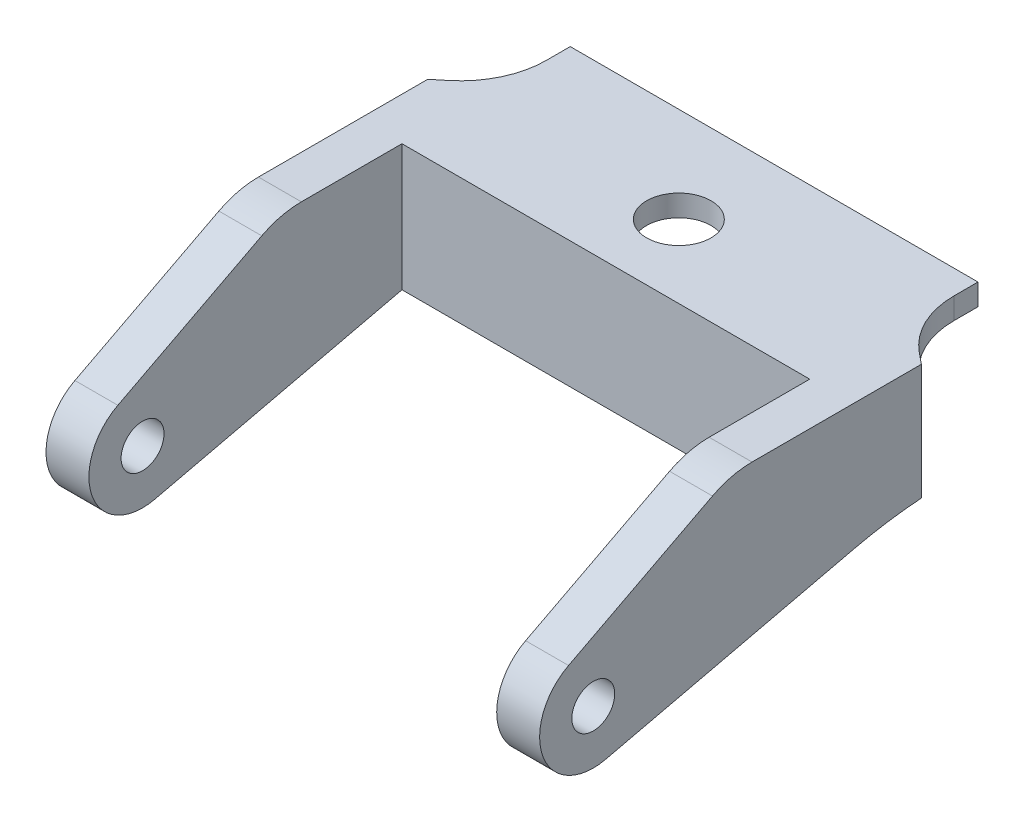
SolidWorks part; units mm, degrees
note: The reader was unsure of these and kept them because the rebuilt part matched: shared geometry of "草图1<7>", "草图1<5>".
ref_plane "前视基准面" through (0, 0, 0) normal (0, 0, 1) x (1, 0, 0)
ref_plane "上视基准面" through (0, 0, 0) normal (0, 1, 0) x (1, 0, 0)
ref_plane "右视基准面" through (0, 0, 0) normal (1, 0, 0) x (0, 0, -1)
sketch "草图1" plane through (0, 0, 0) normal (0, 1, 0) x (1, 0, 0)
  line L1 (39.4264, 36.598) -> (16.3284, 13.5)
  line L4 (42.4264, 36.4264) -> (42.4264, 37.9264) construction
  line L5 (41.4264, 36.4264) -> (41.4264, 37.9264)
  line L10 (43.4264, 36.4264) -> (43.4264, 37.9264)
  line L13 (42.4264, 36.4264) -> (42.4264, 37.9264) construction
  line L17 (39.4264, 36.4264) -> (39.4264, 36.598)
  line L24 (45.4264, 36.4264) -> (45.4264, 39.4264)
  line L27 (0, -52.2528) -> (9.5, -52.2528)
  line L28 (48.4264, 42.4264) -> (46.9264, 42.4264) construction
  line L31 (48.4264, 39.4264) -> (45.4264, 39.4264)
  line L33 (48.4264, 45.4264) -> (45.4264, 45.4264)
  line L34 (48.4264, 42.4264) -> (46.9264, 42.4264) construction
  line L35 (48.4264, 43.4264) -> (46.9264, 43.4264)
  line L44 (48.4264, 41.4264) -> (46.9264, 41.4264)
  line L45 (42.4264, 48.4264) -> (42.4264, 46.9264) construction
  line L48 (36.4264, 42.4264) -> (37.9264, 42.4264) construction
  line L51 (45.4264, 48.4264) -> (45.4264, 45.4264)
  line L54 (39.4264, 48.4264) -> (39.4264, 44.7345)
  line L57 (36.4264, 44.7345) -> (39.4264, 44.7345)
  line L58 (36.4264, 40.1183) -> (36.598, 40.1183)
  line L59 (42.4264, 48.4264) -> (42.4264, 46.9264) construction
  line L62 (43.4264, 48.4264) -> (43.4264, 46.9264)
  line L63 (41.4264, 48.4264) -> (41.4264, 46.9264)
  line L64 (36.4264, 42.4264) -> (37.9264, 42.4264) construction
  line L65 (36.4264, 41.4264) -> (37.9264, 41.4264)
  line L66 (36.4264, 43.4264) -> (37.9264, 43.4264)
  line L67 (17.846, 44.3838) -> (34.1768, 41.9101)
  line L68 (0, 42) -> (10, 42)
  line L69 (0, 40) -> (10, 40)
  line L70 (0, 1) -> (0, 5)
  line L71 (0, 1) -> (10, 1)
  line L72 (0, -1) -> (10, -1)
  line L73 (-1, 0) -> (-4.9453, 0)
  line L77 (7.5, 5) -> (0, 5)
  line L78 (48.4035, 2.9662) -> (43.7435, 33.731)
  line L84 (36.598, 40.1183) -> (17.846, 19.8453)
  line L85 (36.4264, -42.4264) -> (37.9264, -42.4264) construction
  line L87 (42.4264, -48.4264) -> (42.4264, -46.9264) construction
  line L88 (48.4264, -42.4264) -> (46.9264, -42.4264) construction
  line L89 (42.4264, -36.4264) -> (42.4264, -37.9264) construction
  line L92 (41.7553, -33.5024) -> (46.5405, -1.9113)
  line L94 (41.7553, 33.5024) -> (46.5405, 1.9113)
  line L95 (17.846, 19.8453) -> (17.846, 44.3838)
  line L96 (48.4035, -2.9662) -> (43.7435, -33.731)
  line L98 (36.4264, -40.1183) -> (36.598, -40.1183)
  line L99 (2.9662, -48.4035) -> (42.4264, -42.4264)
  line L101 (45.4264, -48.4264) -> (45.4264, -45.4264)
  line L102 (48.4264, -45.4264) -> (45.4264, -45.4264)
  line L103 (48.4264, -39.4264) -> (45.4264, -39.4264)
  line L104 (45.4264, -36.4264) -> (45.4264, -39.4264)
  line L105 (39.4264, -36.4264) -> (39.4264, -36.598)
  line L106 (39.4264, -36.598) -> (16.3284, -13.5)
  line L107 (36.4264, -42.4264) -> (37.9264, -42.4264) construction
  line L108 (36.4264, -41.4264) -> (37.9264, -41.4264)
  line L109 (36.4264, -43.4264) -> (37.9264, -43.4264)
  line L110 (42.4264, -48.4264) -> (42.4264, -46.9264) construction
  line L111 (43.4264, -48.4264) -> (43.4264, -46.9264)
  line L112 (41.4264, -48.4264) -> (41.4264, -46.9264)
  line L113 (48.4264, -42.4264) -> (46.9264, -42.4264) construction
  line L114 (48.4264, -43.4264) -> (46.9264, -43.4264)
  line L115 (48.4264, -41.4264) -> (46.9264, -41.4264)
  line L116 (42.4264, -36.4264) -> (42.4264, -37.9264) construction
  line L117 (41.4264, -36.4264) -> (41.4264, -37.9264)
  line L118 (43.4264, -36.4264) -> (43.4264, -37.9264)
  line L119 (34.531, 43.7435) -> (2.9817, 48.5223)
  line L120 (0, 51.8528) -> (0, 50.3528)
  line L125 (0, 47.3528) -> (0, 42)
  line L126 (0, -47.3528) -> (0, -44.4131)
  line L127 (0, -51.8528) -> (0, -50.3528)
  line L128 (9.5, -44.3838) -> (9.5, -47.4138)
  line L129 (17.846, -44.3838) -> (34.1768, -41.9101)
  line L130 (17.846, -19.8453) -> (17.846, -44.3838)
  line L131 (36.598, -40.1183) -> (17.846, -19.8453)
  line L132 (36.4264, -40.1183) -> (36.598, -40.1183)
  line L133 (0, -29.3528) -> (10, -29.3528)
  line L138 (10, -29.3528) -> (10, -43.3528)
  line L139 (0, -29.3528) -> (0, -1)
  line L140 (8.5, 34) -> (8.5, 20) construction
  line L141 (10, 34) -> (10, 20)
  line L142 (7, 34) -> (7, 20)
  line L143 (3.5, 34) -> (3.5, 15) construction
  line L144 (5, 34) -> (5, 15)
  line L145 (2, 34) -> (2, 15)
  line L146 (16.3284, 13.5) -> (16.3284, -13.5)
  line L147 (7, -26.3528) -> (0, -26.3528)
  line L148 (7.5, 7) -> (0, 7)
  line L149 (0, 7) -> (0, 40)
  line L150 (0, -52.2528) -> (0, -51.8528)
  line L153 (9.5, -52.2528) -> (9.5, -70.2528)
  line L154 (9.5, -70.2528) -> (11.5, -70.2528)
  line L155 (11.5, -70.2528) -> (11.5, -49.0528)
  line L156 (9.5, -44.4131) -> (0, -44.4131)
  line L158 (0, -51.8528) -> (3, -51.8528)
  line L159 (9.5, -47.4138) -> (11.5, -49.0528)
  circle A48 centre (10, 10) radius 1
  circle A49 centre (12.5, 12.5) radius 1
  arc A52 (41.4264, 36.4264) -> (43.4264, 36.4264) centre (42.4264, 36.4264) ccw
  arc A53 (43.4264, 37.9264) -> (41.4264, 37.9264) centre (42.4264, 37.9264) ccw
  arc A54 (39.4264, 36.4264) -> (41.7553, 33.5024) centre (42.4264, 36.4264) ccw
  arc A56 (48.4264, 45.4264) -> (48.4264, 39.4264) centre (48.4264, 42.4264) cw
  arc A57 (48.4264, 43.4264) -> (48.4264, 41.4264) centre (48.4264, 42.4264) cw
  arc A58 (46.9264, 41.4264) -> (46.9264, 43.4264) centre (46.9264, 42.4264) cw
  arc A59 (45.4264, 48.4264) -> (39.4264, 48.4264) centre (42.4264, 48.4264) ccw
  arc A61 (43.4264, 48.4264) -> (41.4264, 48.4264) centre (42.4264, 48.4264) ccw
  arc A62 (41.4264, 46.9264) -> (43.4264, 46.9264) centre (42.4264, 46.9264) ccw
  arc A63 (36.4264, 41.4264) -> (36.4264, 43.4264) centre (36.4264, 42.4264) cw
  arc A64 (37.9264, 43.4264) -> (37.9264, 41.4264) centre (37.9264, 42.4264) cw
  circle A65 centre (42.4264, 42.4264) radius 2.5
  arc A69 (10, 40) -> (10, 42) centre (10, 41) ccw
  arc A71 (10, -1) -> (10, 1) centre (10, 0) ccw
  arc A76 (34.1768, 41.9101) -> (36.4264, 40.1183) centre (36.4264, 42.4264) ccw
  arc A77 (33.5024, -43.0975) -> (36.4264, -45.4264) centre (36.4264, -42.4264) ccw
  arc A79 (0, 50.3528) -> (0, 47.3528) centre (0, 48.8528) cw
  arc A80 (2.9817, 48.5223) -> (0, 51.8528) centre (0, 48.8528) ccw
  circle A81 centre (42.4264, -42.4264) radius 2.5
  arc A82 (36.4264, -40.1183) -> (34.3526, -41.4131) centre (36.4264, -42.4264) ccw
  arc A83 (45.4264, -48.4264) -> (39.4264, -48.4264) centre (42.4264, -48.4264) cw
  arc A84 (48.4264, -45.4264) -> (48.4264, -39.4264) centre (48.4264, -42.4264) ccw
  arc A85 (39.4264, -36.4264) -> (41.7553, -33.5024) centre (42.4264, -36.4264) cw
  circle A86 centre (12.5, -12.5) radius 1
  circle A87 centre (10, -10) radius 1
  arc A88 (36.4264, -41.4264) -> (36.4264, -43.4264) centre (36.4264, -42.4264) ccw
  arc A89 (37.9264, -43.4264) -> (37.9264, -41.4264) centre (37.9264, -42.4264) ccw
  arc A90 (43.4264, -48.4264) -> (41.4264, -48.4264) centre (42.4264, -48.4264) cw
  arc A91 (41.4264, -46.9264) -> (43.4264, -46.9264) centre (42.4264, -46.9264) cw
  arc A92 (48.4264, -43.4264) -> (48.4264, -41.4264) centre (48.4264, -42.4264) ccw
  arc A93 (46.9264, -41.4264) -> (46.9264, -43.4264) centre (46.9264, -42.4264) ccw
  arc A94 (41.4264, -36.4264) -> (43.4264, -36.4264) centre (42.4264, -36.4264) cw
  arc A95 (43.4264, -37.9264) -> (41.4264, -37.9264) centre (42.4264, -37.9264) cw
  circle A99 centre (48.8528, 0) radius 1.5
  arc A101 (48.4035, -2.9662) -> (48.4035, 2.9662) centre (48.8528, 0) ccw
  arc A102 (43.7435, 33.731) -> (45.4264, 36.4264) centre (42.4264, 36.4264) ccw
  arc A103 (46.5405, 1.9113) -> (46.5405, -1.9113) centre (48.8528, 0) ccw
  arc A104 (43.7435, -33.731) -> (45.4264, -36.4264) centre (42.4264, -36.4264) cw
  arc A105 (36.4264, 44.7345) -> (34.531, 43.7435) centre (36.4264, 42.4264) ccw
  arc A107 (0, -50.3528) -> (0, -47.3528) centre (0, -48.8528) ccw
  arc A108 (34.1768, -41.9101) -> (36.4264, -40.1183) centre (36.4264, -42.4264) cw
  circle A109 centre (10, -26.3528) radius 1.5
  arc A110 (10, 34) -> (7, 34) centre (8.5, 34) ccw
  arc A111 (7, 20) -> (10, 20) centre (8.5, 20) ccw
  arc A112 (5, 34) -> (2, 34) centre (3.5, 34) ccw
  arc A113 (2, 15) -> (5, 15) centre (3.5, 15) ccw
  arc A114 (7.5, 5) -> (7.5, 7) centre (7.5, 6) ccw
  arc A118 (10, -29.3528) -> (7, -26.3528) centre (10, -26.3528) ccw
  arc A119 (0, -51.8528) -> (2.9662, -48.4035) centre (0, -48.8528) ccw
  point P0 (8.5, 27)
  point P11 (42.4264, 37.1764)
  point P16 (42.4264, 37.1764)
  point P28 (47.6764, 42.4264)
  point P29 (47.6764, 42.4264)
  point P44 (5, 30)
  point P47 (42.4264, 47.6764)
  point P48 (37.1764, 42.4264)
  point P49 (42.4264, 47.6764)
  point P54 (37.1764, 42.4264)
  point P63 (5, 0)
  point P118 (15.3284, 0)
  point P127 (37.1764, -42.4264)
  point P134 (42.4264, -47.6764)
  point P139 (47.6764, -42.4264)
  point P144 (42.4264, -37.1764)
  point P145 (42.4264, -37.1764)
  point P166 (3.75, 4)
  point P167 (3.5, 24.5)
extrude "凸台-拉伸1" add sketch "草图1" along normal blind 20 and the other way blind 5
extrude "凸台-拉伸2" add sketch "草图1<7>" along normal blind 5.5
sketch "草图1<7>" plane through (0, 0, 0) normal (0, 1, 0) x (1, 0, 0) same geometry as "草图1"
extrude "切除-拉伸1" cut sketch "草图1<5>" along normal blind 4.5 and the other way blind 2
sketch "草图1<5>" plane through (0, 0, 0) normal (0, 1, 0) x (1, 0, 0) same geometry as "草图1"
sketch "草图3" plane through (11.5, 0, 0) normal (1, 0, 0) x (0, 0, -1)
  line L2 (-52.9185, 5.5) -> (-57.9185, 5.5)
  line L3 (-52.9185, 5.5) -> (-52.9185, 0.1515)
  line L5 (-49.9185, 0.1515) -> (-63.7703, -3.0879)
  line L7 (-85.2396, -9.7942) -> (-43.6847, -5.1892)
  line L8 (-52.9185, 5.5) -> (-42.204, 5.5)
  line L9 (-42.204, 5.5) -> (-40.8752, 24.4918)
  line L10 (-40.6496, 24.1433) -> (-83.2666, 28.0955)
  line L11 (-83.2666, 28.0955) -> (-85.2396, -9.7942)
  line L15 (-43.6847, -5.1892) -> (-42.9641, 0.1515)
  line L21 (-52.9185, 0.1515) -> (-42.9641, 0.1515)
  line L22 (-52.9185, 0.1515) -> (-49.9185, 0.1515)
  line L23 (-57.9185, 5.5) -> (-65.4922, 1.5649)
  circle A19 centre (-64.3396, -0.6536) radius 1
  arc A20 (-65.4922, 1.5649) -> (-63.7703, -3.0879) centre (-64.3396, -0.6536) ccw
extrude "切除-拉伸2" cut sketch "草图3" against normal blind 100
fillet "圆角3" radius 20 1 edges at (7.1522, 0.1515, 49.9185)
fillet "圆角8" radius 4 3 edges at (2.9662, 2.3179, 48.4035) (9.5, 5, 47.4138) (10.5, 5.5, 57.9185)
mirror "镜向1" about plane through (0, -5, 0) normal (1, 0, 0) of bodies 112 125 132
